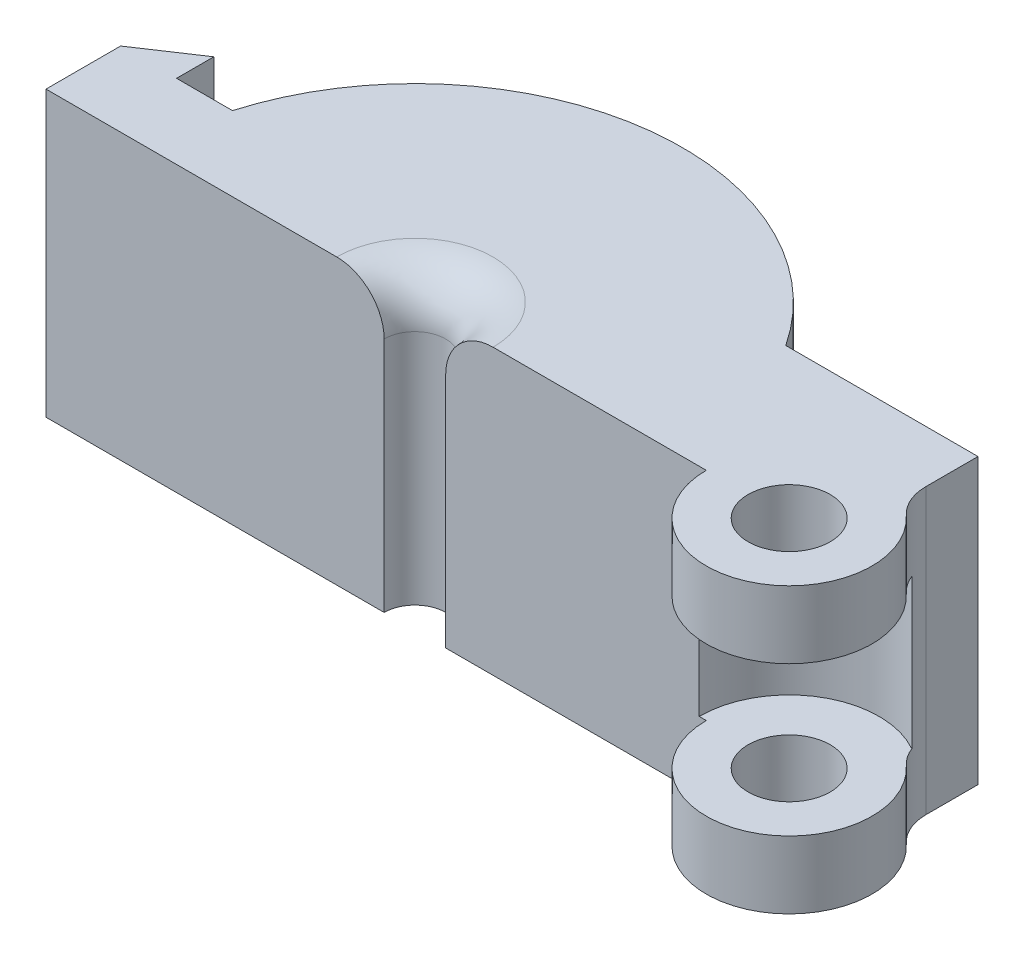
SolidWorks part; units mm, degrees
ref_plane "Front Plane" through (0, 0, 0) normal (0, 0, 1) x (1, 0, 0)
ref_plane "Top Plane" through (0, 0, 0) normal (0, 1, 0) x (1, 0, 0)
ref_plane "Right Plane" through (0, 0, 0) normal (1, 0, 0) x (0, 0, -1)
sketch "Sketch1" plane through (0, 0, 0) normal (0, 1, 0) x (1, 0, 0)
  line L0 (-13.7823, 0) -> (-1.651, 0)
  line L2 (0, 0) -> (0, 14.351) construction
  line L7 (15.625, 0) -> (1.651, 0)
  line L8 (11.9634, 7.9264) -> (22.27, 7.9264)
  line L9 (22.27, 7.9264) -> (22.27, 3.8624)
  line L10 (20.07, 0) -> (22.27, 0) construction
  line L16 (-13.7823, 4) -> (-16.7823, 4)
  line L17 (-19.7823, 0) -> (-19.7823, 4)
  line L18 (-19.7823, 4) -> (-16.7823, 6)
  line L19 (-16.7823, 6) -> (-16.7823, 4)
  line L21 (-13.7823, 0) -> (-19.7823, 0)
  arc A0 (1.651, 0) -> (-1.651, 0) centre (0, 0) ccw
  arc A1 (11.9634, 7.9264) -> (0, 14.351) centre (0, 0) ccw
  arc A3 (15.625, 0) -> (22.27, 3.8624) centre (20.07, 0) ccw
  circle A4 centre (20.07, 0) radius 2.2
  arc A5 (11.9634, 7.9264) -> (-13.7823, 4) centre (0, 0) ccw
  point P1 (0, 0)
  point P4 (-13.4846, 4.911)
  point P9 (-17.351, 7.1501)
  point P12 (-13.7823, 0)
  point P17 (-17.7858, 6)
  point P23 (0, 0)
  dimension "D1" = 3.302
  dimension "D2" = 12.7
  dimension "D5" = 4.445
  dimension "D6" = 3
  dimension "4.1mm" = 4.4
  dimension "D7" = 4
  dimension "D3" = 20.07
  dimension "D4" = 4.064
  dimension "D8" = 2
  dimension "D9" = 3
extrude "Boss-Extrude1" add sketch "Sketch1" along normal blind 15.24 contours A1 A5 L16 L19 L18 L17 L21 L0 A0 L7 A3 L9 L8 A4 region at (2.8883, 0, -5.1959)
ref_plane "Plane1" through (0, 7.62, 0) normal (0, 1, 0) x (1, 0, 0)
sketch "Sketch2" plane through (0, 7.62, 0) normal (0, 1, 0) x (1, 0, 0)
  circle A0 centre (20.07, 0) radius 4.826
  dimension "D1" = 9.652
extrude "Cut-Extrude1" cut sketch "Sketch2" against normal mid plane 8.001
fillet "Fillet1" [suppressed] radius 2.54
fillet "Fillet2" radius 2.54 1 edges at (0, 15.24, -1.651)
fillet "Fillet3" radius 2.54 1 edges at (22.27, 1.8097, -3.8624)
